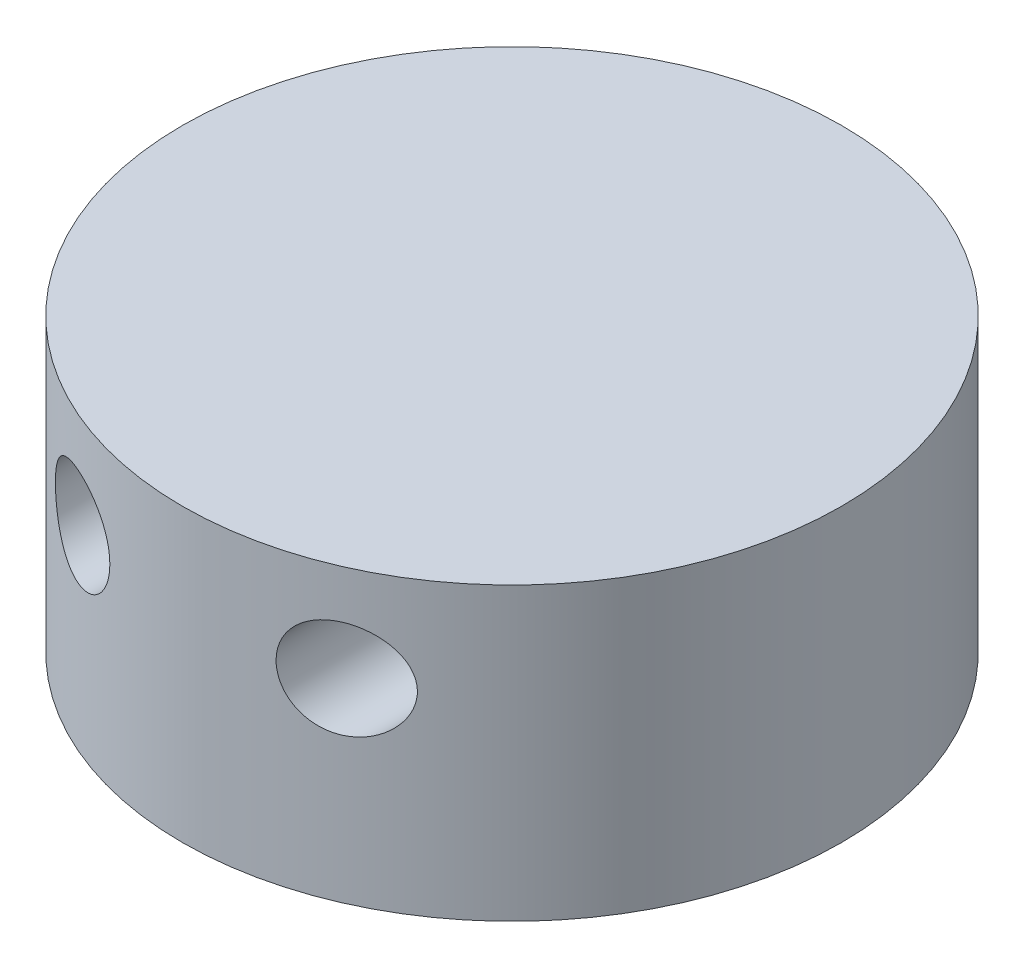
SolidWorks part; units mm, degrees
ref_plane "Front Plane" through (0, 0, 0) normal (0, 0, 1) x (1, 0, 0)
ref_plane "Top Plane" through (0, 0, 0) normal (0, 1, 0) x (1, 0, 0)
ref_plane "Right Plane" through (0, 0, 0) normal (1, 0, 0) x (0, 0, -1)
sketch "Sketch1" plane through (0, 0, 0) normal (0, 1, 0) x (1, 0, 0)
  circle A0 centre (0, 0) radius 21.5646
  dimension "D1" = 43.1292
extrude "Extrude1" add sketch "Sketch1" against normal blind 19.05
sketch "Sketch3" plane through (0, 0, 0) normal (0, 1, 0) x (1, 0, 0)
  line L0 (0, 0) -> (0, 21.5646) construction
  circle A0 centre (0, 0) radius 21.5646 construction
  point P6 (0, 17.2466)
  dimension "D1" = 17.2466
ref_axis "Axis1" through (0, 0, 0) along (0, 1, 0)
ref_plane "Plane1" through (0, 0, -21.59) normal (0, 0, 1) x (1, 0, 0)
sketch "Sketch5" plane through (0, 0, -21.59) normal (0, 0, 1) x (1, 0, 0)
  line L0 (0, 0) -> (0, -19.05) construction
  line L1 (-21.5646, -19.05) -> (21.5646, -19.05) construction
  line L2 (19.8847, -6.35) -> (-18.7057, -6.35) construction
  line L3 (21.5646, 0) -> (-21.5646, 0) construction
  circle A0 centre (8.6371, -6.35) radius 3.2004
  circle A1 centre (-8.6371, -6.35) radius 3.2004
  point P7 (8.6371, -6.35)
  point P8 (-8.6371, -6.35)
  dimension "D3" = 6.4008
  dimension "D4" = 6.4008
  dimension "D1" = 6.35
  dimension "D2" = 8.6371
extrude "Extrude2" cut sketch "Sketch5" along normal through all
